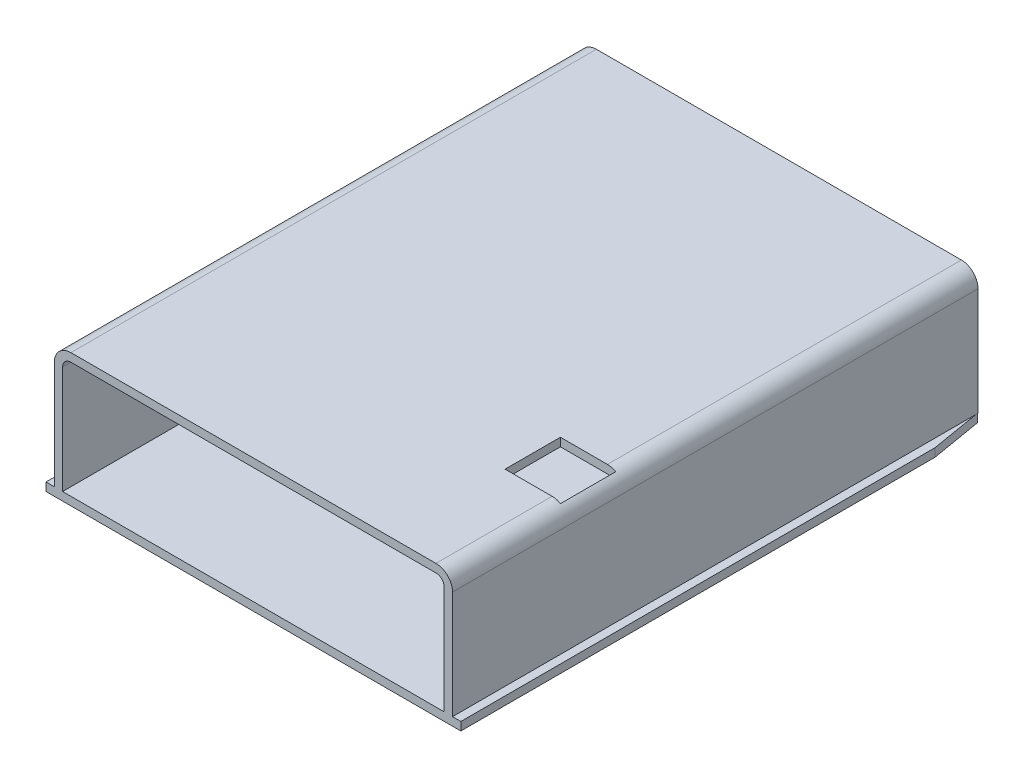
SolidWorks part; units mm, degrees
ref_plane "Front Plane" through (0, 0, 0) normal (0, 0, 1) x (1, 0, 0)
ref_plane "Top Plane" through (0, 0, 0) normal (0, 1, 0) x (1, 0, 0)
ref_plane "Right Plane" through (0, 0, 0) normal (1, 0, 0) x (0, 0, -1)
sketch "Sketch1" plane through (0, 0, 0) normal (0, 0, 1) x (1, 0, 0)
  line L1 (0, 0) -> (72, 0)
  line L2 (0, 0) -> (0, 24)
  line L3 (0, 24) -> (72, 24)
  line L4 (72, 0) -> (72, 24)
  dimension "D1" = 72
  dimension "D2" = 24
extrude "Boss-Extrude1" add sketch "Sketch1" along normal blind 95
sketch "Sketch2" plane through (0, 0, 95) normal (0, 0, 1) x (1, 0, 0)
  line L0 (72, 24) -> (0, 24) construction
  line L1 (1.5, 22.5) -> (70.5, 22.5)
  line L2 (1.5, 22.5) -> (1.5, 1.5)
  line L3 (1.5, 1.5) -> (70.5, 1.5)
  line L4 (70.5, 22.5) -> (70.5, 1.5)
  line L5 (0, 24) -> (0, 0) construction
  line L6 (0, 0) -> (72, 0) construction
  line L7 (72, 0) -> (72, 24) construction
  dimension "D1" = 1.5
  dimension "D2" = 1.5
  dimension "D3" = 1.5
  dimension "D4" = 1.5
extrude "Cut-Extrude1" cut sketch "Sketch2" against normal blind 93
sketch "Sketch3" plane through (0, 24, 0) normal (0, 1, 0) x (1, 0, 0)
  line L1 (60.5, -64) -> (70.5, -64)
  line L2 (60.5, -64) -> (60.5, -74)
  line L3 (60.5, -74) -> (70.5, -74)
  line L4 (70.5, -64) -> (70.5, -74)
  line L6 (72, -95) -> (72, 0) construction
  line L7 (72, -95) -> (0, -95) construction
  dimension "D1" = 10
  dimension "D2" = 10
  dimension "D3" = 1.5
  dimension "D4" = 31
extrude "Cut-Extrude2" cut sketch "Sketch3" against normal blind 2
sketch "Sketch4" plane through (0, 0, 2) normal (0, 0, 1) x (1, 0, 0)
  line L1 (1.5, 22.5) -> (29.24, 22.5)
  line L2 (1.5, 22.5) -> (1.5, 17.5)
  line L3 (1.5, 17.5) -> (29.24, 17.5)
  line L4 (29.24, 22.5) -> (29.24, 17.5)
  dimension "D1" = 5
  dimension "D2" = 27.74
extrude "Boss-Extrude2" add sketch "Sketch4" along normal blind 14
sketch "Sketch5" plane through (0, 0, 0) normal (0, 0, -1) x (-1, 0, 0)
  line L0 (-72, 24) -> (0, 24) construction
  line L1 (-1.5, 22.5) -> (-27.24, 22.5)
  line L2 (-1.5, 22.5) -> (-1.5, 19.5)
  line L3 (-1.5, 19.5) -> (-27.24, 19.5)
  line L4 (-27.24, 22.5) -> (-27.24, 19.5)
  line L5 (0, 24) -> (0, 0) construction
  dimension "D1" = 3
  dimension "D2" = 1.5
  dimension "D3" = 1.5
  dimension "D4" = 25.74
extrude "Cut-Extrude3" cut sketch "Sketch5" against normal blind 16
sketch "Sketch6" plane through (0, 0, 0) normal (0, 0, -1) x (-1, 0, 0)
  line L0 (0, 0) -> (-72, 0) construction
  line L1 (-72, 1.5) -> (-73.5, 1.5)
  line L2 (-72, 1.5) -> (-72, 0)
  line L3 (-72, 0) -> (-73.5, 0)
  line L4 (-73.5, 1.5) -> (-73.5, 0)
  line L5 (0, 1.5) -> (1.5, 1.5)
  line L6 (0, 1.5) -> (0, 0)
  line L7 (0, 0) -> (1.5, 0)
  line L8 (1.5, 1.5) -> (1.5, 0)
  dimension "D1" = 1.5
  dimension "D2" = 1.5
  dimension "D3" = 1.5
  dimension "D4" = 1.5
  dimension "D5" = 0
  dimension "D6" = 0
extrude "Boss-Extrude4" add sketch "Sketch6" against normal blind 95
fillet "Fillet1" radius 3 2 edges at (0, 24, 47.5) (72, 24, 47.5)
sketch "Sketch7" plane through (0, 0, 16) normal (0, 0, 1) x (1, 0, 0)
  line L0 (1.5, 17.5) -> (29.24, 17.5) construction
  line L1 (29.24, 22.5) -> (26.24, 22.5)
  line L2 (29.24, 22.5) -> (29.24, 17.5)
  line L3 (29.24, 17.5) -> (26.24, 17.5)
  line L4 (26.24, 22.5) -> (26.24, 19.5)
  line L5 (27.24, 19.5) -> (1.5, 19.5) construction
  line L6 (1.5, 17.5) -> (3.1, 17.5)
  line L7 (1.5, 17.5) -> (1.5, 22.5)
  line L8 (1.5, 22.5) -> (3.1, 22.5)
  line L9 (3.1, 19.5) -> (3.1, 22.5)
  line L10 (26.24, 17.5) -> (3.1, 17.5)
  line L12 (26.24, 19.5) -> (3.1, 19.5)
  dimension "D1" = 3
  dimension "D2" = 1.6
  dimension "D3" = 1.6
  dimension "D4" = 3
extrude "Boss-Extrude5" add sketch "Sketch7" along normal blind 1
fillet "Fillet2" radius 1.5 3 edges at (70.5, 22.5, 84.5) (70.5, 22.5, 33) (1.5, 22.5, 56)
sketch "Sketch8" plane through (0, 0, 0) normal (0, -1, 0) x (-1, 0, 0)
  line L0 (0, 0) -> (1.5, -9.269)
  line L1 (1.5, -95) -> (1.5, 0) construction
  line L2 (1.5, -9.269) -> (1.5, 0)
  line L3 (1.5, 0) -> (0, 0)
  line L4 (-73.5, -9.269) -> (-71.9348, 0)
  line L5 (-73.5, -95) -> (-73.5, 0) construction
  line L6 (1.5, 0) -> (-73.5, 0) construction
  line L7 (-71.9348, 0) -> (-73.5, 0)
  line L8 (-73.5, 0) -> (-73.5, -9.269)
extrude "Cut-Extrude4" cut sketch "Sketch8" against normal blind 1.5
